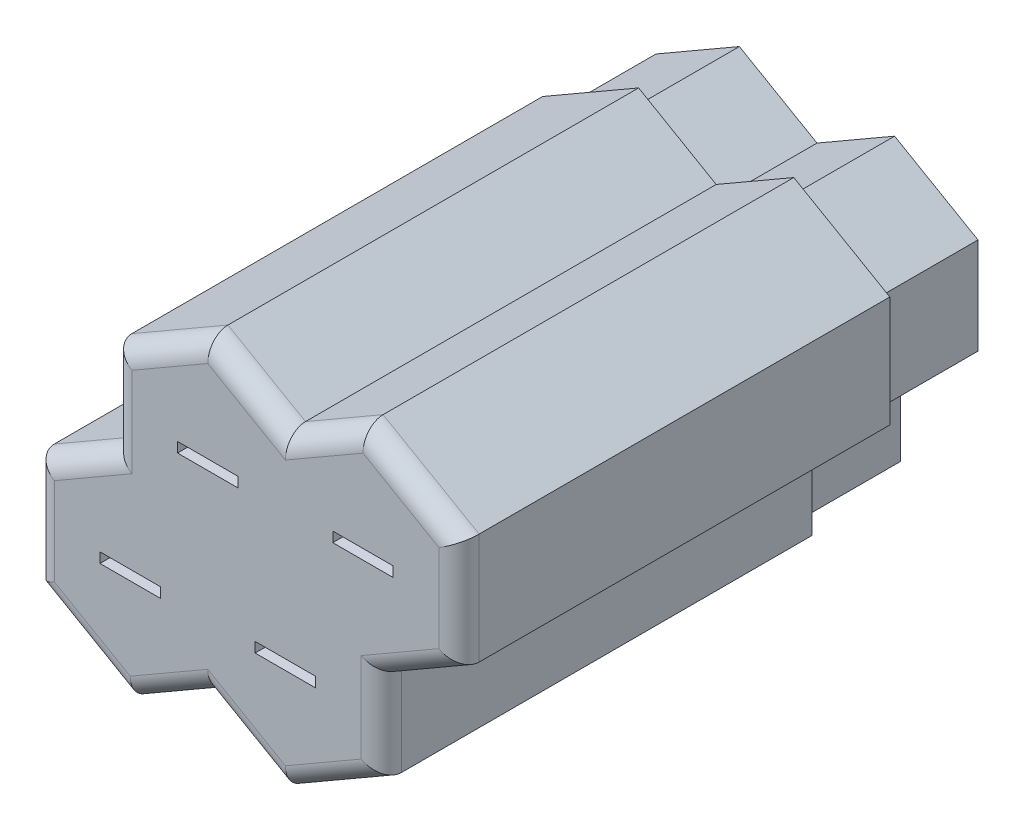
SolidWorks part; units mm, degrees
ref_plane "Ön Düzlem" through (0, 0, 0) normal (0, 0, 1) x (1, 0, 0)
ref_plane "Üst Düzlem" through (0, 0, 0) normal (0, 1, 0) x (1, 0, 0)
ref_plane "Sağ Düzlem" through (0, 0, 0) normal (1, 0, 0) x (0, 0, -1)
sketch "Sketch2" plane through (0, 0, 0) normal (0, 0, 1) x (1, 0, 0)
  line L0 (0, 0) -> (-9.5263, 5.5) construction
  line L1 (0, 11) -> (-9.5263, 5.5)
  line L2 (-9.5263, 5.5) -> (-9.5263, -5.5)
  line L3 (-9.5263, -5.5) -> (0, -11)
  line L4 (0, -11) -> (9.5263, -5.5)
  line L5 (9.5263, -5.5) -> (9.5263, 5.5)
  line L6 (9.5263, 5.5) -> (0, 11)
  line L7 (3, -0.5) -> (-3, -0.5)
  line L8 (3, -0.5) -> (3, 0.5)
  line L9 (3, 0.5) -> (-3, 0.5)
  line L10 (-3, -0.5) -> (-3, 0.5)
  line L11 (3, -0.5) -> (-3, 0.5) construction
  line L12 (3, 0.5) -> (-3, -0.5) construction
  line L13 (2.801, -10.5083) -> (7.7, -7.6799)
  line L14 (0, 0) -> (0, -11) construction
  line L15 (0, 0) -> (9.5263, -5.5) construction
  line L16 (15.4, 5.6569) -> (10.501, 2.8285)
  line L17 (0, 0) -> (0, 11) construction
  line L18 (10.501, 2.8285) -> (10.501, -2.8285)
  line L19 (10.501, -2.8285) -> (15.4, -5.6569)
  line L20 (15.4, -5.6569) -> (20.299, -2.8285)
  line L21 (20.299, -2.8285) -> (20.299, 2.8285)
  line L22 (20.299, 2.8285) -> (15.4, 5.6569)
  line L23 (0, 5.6569) -> (-4.899, 2.8285)
  line L24 (-4.899, 2.8285) -> (-4.899, -2.8285)
  line L25 (-4.899, -2.8285) -> (0, -5.6569)
  line L26 (-1.8263, -7.8368) -> (-1.8263, -18.8368)
  line L27 (0, -5.6569) -> (4.899, -2.8285)
  line L28 (4.899, -2.8285) -> (4.899, 2.8285)
  line L29 (4.899, 2.8285) -> (0, 5.6569)
  line L30 (7.7, -13.3368) -> (7.7, -2.3368) construction
  line L31 (7.7, -13.3368) -> (7.7, -24.3368) construction
  line L32 (2.801, -16.1653) -> (2.801, -10.5083)
  line L33 (7.7, 0) -> (7.7, 14.7115) construction
  line L34 (-9.5263, 2.8285) -> (9.5263, 2.8285)
  line L35 (-9.5263, 2.8285) -> (-9.5263, -2.8285)
  line L36 (7.7, -18.9937) -> (2.801, -16.1653)
  line L37 (-9.5263, -2.8285) -> (9.5263, -2.8285)
  line L38 (9.5263, 2.8285) -> (9.5263, -2.8285)
  line L39 (12.599, -16.1653) -> (7.7, -18.9937)
  line L40 (12.599, -10.5083) -> (12.599, -16.1653)
  line L41 (7.7, -7.6799) -> (12.599, -10.5083)
  line L42 (12.4, -0.5) -> (12.4, -9.2679) construction
  line L43 (7.7, -2.3368) -> (-1.8263, -7.8368)
  line L44 (17.2263, -7.8368) -> (7.7, -2.3368)
  line L45 (17.2263, -18.8368) -> (17.2263, -7.8368)
  line L46 (7.7, -24.3368) -> (17.2263, -18.8368)
  line L47 (-1.8263, -18.8368) -> (7.7, -24.3368)
  line L48 (10.7, -13.8368) -> (4.7, -12.8368) construction
  line L49 (10.7, -12.8368) -> (4.7, -13.8368) construction
  line L50 (4.698, -12.837) -> (10.698, -13.837) construction
  line L51 (4.698, -13.837) -> (10.698, -12.837) construction
  line L52 (4.7, -12.8368) -> (4.7, -13.8368)
  line L53 (10.7, -13.8368) -> (4.7, -13.8368)
  line L54 (10.7, -12.8368) -> (10.7, -13.8368)
  line L55 (10.7, -12.8368) -> (4.7, -12.8368)
  line L56 (18.402, -0.4998) -> (12.402, 0.5002) construction
  line L57 (18.402, 0.5002) -> (12.402, -0.4998) construction
  line L58 (10.698, -13.837) -> (10.698, -12.837)
  line L59 (4.698, -12.837) -> (10.698, -12.837)
  line L60 (4.698, -13.837) -> (4.698, -12.837)
  line L61 (4.698, -13.837) -> (10.698, -13.837)
  line L62 (-3.002, 0.5002) -> (2.998, 0.5002)
  line L63 (-3.002, 0.5002) -> (-3.002, -0.4998)
  line L64 (-3.002, -0.4998) -> (2.998, -0.4998)
  line L65 (2.998, 0.5002) -> (2.998, -0.4998)
  line L66 (-3.002, 0.5002) -> (2.998, -0.4998) construction
  line L67 (-3.002, -0.4998) -> (2.998, 0.5002) construction
  line L68 (-7.7, -13.3368) -> (-7.7, -2.3368) construction
  line L69 (-4.698, -13.837) -> (-10.698, -12.837) construction
  line L70 (-4.698, -12.837) -> (-10.698, -13.837) construction
  line L71 (-10.7, -12.8368) -> (-4.7, -13.8368) construction
  line L72 (-10.7, -13.8368) -> (-4.7, -12.8368) construction
  line L73 (-4.698, -13.837) -> (-10.698, -13.837)
  line L74 (-4.698, -13.837) -> (-4.698, -12.837)
  line L75 (-4.698, -12.837) -> (-10.698, -12.837)
  line L76 (-10.698, -13.837) -> (-10.698, -12.837)
  line L77 (-10.7, -12.8368) -> (-4.7, -12.8368)
  line L78 (-10.7, -12.8368) -> (-10.7, -13.8368)
  line L79 (-10.7, -13.8368) -> (-4.7, -13.8368)
  line L80 (-4.7, -12.8368) -> (-4.7, -13.8368)
  line L81 (-12.599, -16.1653) -> (-7.7, -18.9937)
  line L82 (15.4, 0) -> (15.4, 11) construction
  line L83 (-7.7, -18.9937) -> (-2.801, -16.1653)
  line L84 (15.4, 0) -> (5.8737, -5.5) construction
  line L85 (15.4, 0) -> (15.4, -11) construction
  line L86 (-2.801, -16.1653) -> (-2.801, -10.5083)
  line L87 (12.4, 0.5) -> (18.4, -0.5) construction
  line L88 (12.4, -0.5) -> (18.4, 0.5) construction
  line L89 (15.4, 0) -> (24.9263, 5.5) construction
  line L90 (-2.801, -10.5083) -> (-7.7, -7.6799)
  line L91 (12.402, 0.5002) -> (12.402, -0.4998)
  line L92 (18.402, -0.4998) -> (12.402, -0.4998)
  line L93 (18.402, 0.5002) -> (18.402, -0.4998)
  line L94 (18.402, 0.5002) -> (12.402, 0.5002)
  line L95 (-7.7, -7.6799) -> (-12.599, -10.5083)
  line L96 (-12.599, -10.5083) -> (-12.599, -16.1653)
  line L97 (-17.2263, -7.8368) -> (-7.7, -2.3368)
  line L98 (-7.7, -2.3368) -> (1.8263, -7.8368)
  line L99 (1.8263, -7.8368) -> (1.8263, -18.8368)
  line L100 (-7.7, -13.3368) -> (-7.7, -24.3368) construction
  line L101 (1.8263, -18.8368) -> (-7.7, -24.3368)
  line L102 (-7.7, -24.3368) -> (-17.2263, -18.8368)
  line L103 (-17.2263, -18.8368) -> (-17.2263, -7.8368)
  line L104 (18.402, -0.4998) -> (10.7, -13.8368)
  line L105 (-3.002, -0.4998) -> (-10.7, -12.8368)
  line L107 (17.2263, -10.5083) -> (-17.2263, -10.5083)
  line L108 (17.2263, -10.5083) -> (17.2263, -16.1653)
  line L109 (17.2263, -16.1653) -> (-17.2263, -16.1653)
  line L110 (5.8737, 2.8285) -> (5.8737, -2.8285)
  line L111 (24.9263, -2.8285) -> (5.8737, -2.8285)
  line L112 (-17.2263, -10.5083) -> (-17.2263, -16.1653)
  line L114 (24.9263, 2.8285) -> (24.9263, -2.8285)
  line L115 (-3.002, -0.4998) -> (-3.002, -9.2668) construction
  line L116 (3, -0.5) -> (3, -9.2679) construction
  line L117 (24.9263, 2.8285) -> (5.8737, 2.8285)
  line L121 (18.4, -0.5) -> (18.4, 0.5)
  line L122 (12.4, 0.5) -> (18.4, 0.5)
  line L123 (12.4, -0.5) -> (12.4, 0.5)
  line L124 (12.4, -0.5) -> (18.4, -0.5)
  line L125 (5.8737, 5.5) -> (15.4, 11)
  line L126 (5.8737, -5.5) -> (5.8737, 5.5)
  line L127 (15.4, -11) -> (5.8737, -5.5)
  line L128 (24.9263, -5.5) -> (15.4, -11)
  line L129 (24.9263, 5.5) -> (24.9263, -5.5)
  line L130 (15.4, 11) -> (24.9263, 5.5)
  line L169 (2.3479, -1.9335) -> (-2.8483, 1.0665) [skipped]
  line L170 (2.8479, -1.0675) -> (-2.3483, 1.9325) [skipped]
  line L171 (-2.8483, 1.0665) -> (-2.3483, 1.9325) [skipped]
  line L172 (-0.5011, -3.0009) -> (0.4989, -3.0009) [skipped]
  line L173 (-1.9346, -2.3487) -> (-1.0686, -2.8487) [skipped]
  line L174 (-2.85, -1.0673) -> (-2.35, -1.9333) [skipped]
  line L175 (-2.85, -1.0673) -> (2.3462, 1.9327) [skipped]
  line L176 (-2.35, -1.9333) -> (2.8462, 1.0667) [skipped]
  line L177 (2.348, 1.9335) -> (-2.8481, -1.0665) [skipped]
  line L178 (-2.3481, -1.9325) -> (-2.8481, -1.0665) [skipped]
  line L179 (-1.9346, -2.3487) -> (1.0654, 2.8474) [skipped]
  line L180 (-1.0686, -2.8487) -> (1.9314, 2.3474) [skipped]
  line L181 (-0.5011, -3.0009) -> (-0.5011, 2.9991) [skipped]
  line L182 (0.4989, -3.0009) -> (0.4989, 2.9991) [skipped]
  line L183 (1.0664, -2.8489) -> (-1.9336, 2.3473) [skipped]
  line L184 (-2.8499, 1.0677) -> (2.3463, -1.9323) [skipped]
  line L185 (1.9324, -2.3489) -> (-1.0676, 2.8473) [skipped]
  line L186 (-2.3499, 1.9337) -> (2.8463, -1.0663) [skipped]
  line L187 (2.3462, 1.9327) -> (2.8462, 1.0667) [skipped]
  line L188 (1.0654, 2.8474) -> (1.9314, 2.3474) [skipped]
  line L189 (-0.5011, 2.9991) -> (0.4989, 2.9991) [skipped]
  line L190 (-1.9336, 2.3473) -> (-1.0676, 2.8473) [skipped]
  line L191 (-2.3499, 1.9337) -> (-2.8499, 1.0677) [skipped]
  line L192 (1.0666, 2.849) -> (-1.9334, -2.3472) [skipped]
  line L193 (1.9326, 2.349) -> (-1.0674, -2.8472) [skipped]
  line L194 (2.848, 1.0675) -> (2.348, 1.9335) [skipped]
  line L195 (-2.35, -1.9333) -> (2.3462, 1.9327) construction
  line L196 (2.848, 1.0675) -> (-2.3481, -1.9325) [skipped]
  line L197 (-2.85, -1.0673) -> (2.8462, 1.0667) construction
  line L198 (2.848, 1.0675) -> (-2.8481, -1.0665) construction
  line L199 (2.348, 1.9335) -> (-2.3481, -1.9325) construction
  line L200 (0.4991, 3.0011) -> (0.4991, -2.9989) [skipped]
  line L201 (-0.5011, -3.0009) -> (0.4989, 2.9991) construction
  line L202 (-1.9346, -2.3487) -> (1.9314, 2.3474) construction
  line L203 (-1.0686, -2.8487) -> (1.0654, 2.8474) construction
  line L204 (0.4991, 3.0011) -> (-0.5009, -2.9989) construction
  line L205 (1.9326, 2.349) -> (-1.9334, -2.3472) construction
  line L206 (1.0666, 2.849) -> (-1.0674, -2.8472) construction
  line L207 (1.9326, 2.349) -> (1.0666, 2.849) [skipped]
  line L208 (0.4991, 3.0011) -> (-0.5009, 3.0011) [skipped]
  line L209 (-1.0684, 2.8491) -> (1.9316, -2.347) [skipped]
  line L210 (-1.0684, 2.8491) -> (-1.9344, 2.3491) [skipped]
  line L211 (-1.9344, 2.3491) -> (1.0656, -2.847) [skipped]
  line L212 (-0.5009, 3.0011) -> (-0.5009, -2.9989) [skipped]
  line L213 (2.3479, -1.9335) -> (-2.3483, 1.9325) construction
  line L214 (1.0664, -2.8489) -> (-1.0676, 2.8473) construction
  line L215 (1.9324, -2.3489) -> (-1.9336, 2.3473) construction
  line L216 (0.4989, -3.0009) -> (-0.5011, 2.9991) construction
  line L217 (-2.3499, 1.9337) -> (2.3463, -1.9323) construction
  line L218 (-1.0684, 2.8491) -> (1.0656, -2.847) construction
  line L219 (-1.9344, 2.3491) -> (1.9316, -2.347) construction
  line L220 (-0.5009, 3.0011) -> (0.4991, -2.9989) construction
  line L221 (2.8479, -1.0675) -> (-2.8483, 1.0665) construction
  line L222 (-2.8499, 1.0677) -> (2.8463, -1.0663) construction
  line L223 (2.3479, -1.9335) -> (2.8479, -1.0675) [skipped]
  line L224 (2.8463, -1.0663) -> (2.3463, -1.9323) [skipped]
  line L225 (1.0664, -2.8489) -> (1.9324, -2.3489) [skipped]
  line L226 (0.4991, -2.9989) -> (-0.5009, -2.9989) [skipped]
  line L227 (-1.0674, -2.8472) -> (-1.9334, -2.3472) [skipped]
  line L228 (1.9316, -2.347) -> (1.0656, -2.847) [skipped]
  circle A0 centre (0, 0) radius 4.899 construction
  circle A1 centre (0, 0) radius 7.7
  circle A2 centre (15.4, 0) radius 5.6569
  circle A3 centre (15.4, 0) radius 7.7
  circle A4 centre (0, 0) radius 5.6569
  circle A5 centre (7.7, -13.3368) radius 4.899 construction
  circle A6 centre (7.7, -13.3368) radius 5.6569
  circle A7 centre (7.7, -13.3368) radius 7.7
  circle A8 centre (-7.7, -13.3368) radius 4.899 construction
  circle A9 centre (-7.7, -13.3368) radius 5.6569
  circle A10 centre (15.4, 0) radius 4.899 construction
  circle A11 centre (-7.7, -13.3368) radius 7.7
  dimension "D1" = 15.4
  dimension "D3" = 6
  dimension "D6" = 12
extrude "Boss-Extrude1" add sketch "Sketch2" along normal blind 2.25 contours L128 L127 L126 L125 L130 L129 | L2 L3 L4 L5 L6 L1 | L9 L10 L7 L8 | L94 L91 L92 L93 | L103 L97 L98 L99 L101 L102 | L47 L46 L45 L44 L43 L26 | L54 L55 L52 L53 | L75 L76 L73 L74
extrude "Boss-Extrude2" add sketch "Sketch2<4>" against normal blind 50.5 contours L5 A3 L117 L129 L130 L125 L6 | A1 L126 L125 L6 L1 L2 L34 | L117 A3 L111 L114 | L111 A3 L44 L45 L128 L129 | A7 L127 L128 L45 L44 A3 L104 | A7 L99 L101 L47 L46 L45 L128 L127 | A7 A11 L26 L47 L101 L99 | L26 A11 L3 L2 L97 L103 L102 L101 L47 | A1 L34 L2 L37 L97 L98 | L3 A11 L105 A1 L37 L97 L2 | L117 A3 L5 L6 L125 L126 A1 | A7 L4 L5 A3 L111 A1 L126 L127 | L26 A11 L3 L4 A7 L99 L98 A1 L43 | A1 L98 L97 L37 | L2 L97 L37 | A7 L109 L45 L107 L128 L127 | L109 A11 L107 L103 | L107 A11 L3 L2 L97 L103 | L111 A3 L44 L43 A1 | L107 A11 L3 L4 A7 | A7 L127 L128 L107 | L45 L128 L107 region at (3.7547, 8.6121, 0) region at (11.6453, 8.6121, 0) region at (7.7, 4.753, 0) region at (-8.5449, 0.0928, 0) region at (-9.2014, -3.016, 0) region at (-7.918, -4.3988, 0) region at (-13.7224, -7.2572, 0) region at (-7.7583, -2.6563, 0) region at (23.9184, 0, 0) region at (21.4224, -6.0796, 0) region at (-16.2184, -13.3368, 0) region at (7.7, -2.6464, 0) region at (-16.044, -16.3559, 0) region at (7.7, -4.5314, 0) region at (15.6804, -8.9709, 0) region at (16.9014, -10.3207, 0) region at (0, -8.8053, 0) region at (16.2449, -13.4295, 0) region at (15.4583, -10.6805, 0) region at (0, -18.0898, 0) region at (0, -10.6904, 0) region at (17.0356, -17.501, 0)
sketch "Sketch2<4>" plane through (0, 0, 0) normal (0, 0, 1) x (1, 0, 0) same geometry as "Sketch2"
extrude "Cut-Extrude1" cut sketch "Sketch2<5>" along normal blind 0.25 contours A2 | A4 | A6 | A9
sketch "Sketch2<5>" plane through (0, 0, 0) normal (0, 0, 1) x (1, 0, 0) same geometry as "Sketch2"
fillet "Fillet1" radius 2 14 edges at (3.85, 8.7772, 2.25) (20.1631, 8.25, 2.25) (11.55, 8.7772, 2.25) (24.9263, 0, 2.25) (21.0763, -7.7228, 2.25) (17.2263, -14.3912, 2.25) (12.4631, -21.5868, 2.25) (3.85, -22.114, 2.25) (-3.85, -22.114, 2.25) (-12.4631, -21.5868, 2.25) (-17.2263, -13.3368, 2.25) (-13.3763, -5.614, 2.25) (-9.5263, 1.0544, 2.25) (-4.7631, 8.25, 2.25)
sketch "Sketch7" plane through (0, 0, -50.5) normal (0, 0, -1) x (-1, 0, 0)
  line L0 (-24.9263, 5.5) -> (-24.9263, -5.5)
  line L1 (-7.7, 5.111) -> (-15.4, 9.5566)
  line L2 (-15.4, 9.5566) -> (-23.6763, 4.7783)
  line L3 (-23.6763, 4.7783) -> (-23.6763, -4.7783)
  line L4 (-23.6763, -4.7783) -> (-15.9763, -9.2239)
  line L5 (-15.9763, -18.1151) -> (-15.9763, -9.2239)
  line L6 (-7.7, -22.8934) -> (-15.9763, -18.1151)
  line L7 (0, -18.4478) -> (-7.7, -22.8934)
  line L8 (0, -18.4478) -> (7.7, -22.8934)
  line L9 (7.7, -22.8934) -> (15.9763, -18.1151)
  line L10 (15.9763, -18.1151) -> (15.9763, -8.5585)
  line L11 (15.9763, -8.5585) -> (8.2763, -4.1129)
  line L12 (8.2763, 4.7783) -> (8.2763, -4.1129)
  line L13 (0, 9.5566) -> (8.2763, 4.7783)
  line L14 (-7.7, 5.111) -> (0, 9.5566)
  line L130 (-12.4, -0.5) -> (-18.4, 0.5) construction
  line L131 (-12.4, 0.5) -> (-18.4, -0.5) construction
  line L135 (10.7, -13.8368) -> (4.7, -12.8368) construction
  line L136 (10.7, -12.8368) -> (4.7, -13.8368) construction
  line L137 (4.698, -12.837) -> (10.698, -13.837) construction
  line L138 (4.698, -13.837) -> (10.698, -12.837) construction
  line L140 (3.002, -0.4998) -> (-2.998, 0.5002) construction
  line L141 (3.002, 0.5002) -> (-2.998, -0.4998) construction
  line L142 (-18.402, 0.5002) -> (-12.402, -0.4998) construction
  line L143 (-18.402, -0.4998) -> (-12.402, 0.5002) construction
  line L144 (-4.698, -13.837) -> (-10.698, -12.837) construction
  line L145 (-4.698, -12.837) -> (-10.698, -13.837) construction
  line L146 (-10.7, -12.8368) -> (-4.7, -13.8368) construction
  line L147 (-10.7, -13.8368) -> (-4.7, -12.8368) construction
  line L155 (-3, 0.5) -> (3, -0.5) construction
  line L156 (-3, -0.5) -> (3, 0.5) construction
  line L158 (-15.4, 11) -> (-24.9263, 5.5)
  line L159 (-24.9263, -5.5) -> (-17.2263, -9.9456)
  line L162 (-7.7, 6.5544) -> (-15.4, 11)
  line L163 (-12.4, -0.5) -> (-18.4, -0.5)
  line L164 (-12.4, -0.5) -> (-12.4, 0.5)
  line L165 (-12.4, 0.5) -> (-18.4, 0.5)
  line L166 (-18.4, -0.5) -> (-18.4, 0.5)
  line L174 (17.2263, -18.8368) -> (17.2263, -7.8368)
  line L175 (7.7, -24.3368) -> (17.2263, -18.8368)
  line L176 (0, -19.8912) -> (7.7, -24.3368)
  line L179 (17.2263, -7.8368) -> (9.5263, -3.3912)
  line L180 (12.599, -10.5083) -> (12.599, -16.1653)
  line L181 (7.7, -7.6799) -> (12.599, -10.5083)
  line L182 (-18.402, 0.5002) -> (-12.402, 0.5002)
  line L183 (-18.402, 0.5002) -> (-18.402, -0.4998)
  line L184 (-18.402, -0.4998) -> (-12.402, -0.4998)
  line L185 (-12.402, 0.5002) -> (-12.402, -0.4998)
  line L186 (2.801, -10.5083) -> (7.7, -7.6799)
  line L187 (2.801, -16.1653) -> (2.801, -10.5083)
  line L188 (7.7, -18.9937) -> (2.801, -16.1653)
  line L189 (12.599, -16.1653) -> (7.7, -18.9937)
  line L190 (4.7, -12.8368) -> (4.7, -13.8368)
  line L191 (10.7, -13.8368) -> (4.7, -13.8368)
  line L192 (10.7, -12.8368) -> (10.7, -13.8368)
  line L193 (10.7, -12.8368) -> (4.7, -12.8368)
  line L194 (10.698, -13.837) -> (10.698, -12.837)
  line L195 (4.698, -12.837) -> (10.698, -12.837)
  line L196 (4.698, -13.837) -> (4.698, -12.837)
  line L197 (4.698, -13.837) -> (10.698, -13.837)
  line L198 (-2.998, 0.5002) -> (-2.998, -0.4998)
  line L199 (3.002, -0.4998) -> (-2.998, -0.4998)
  line L200 (3.002, 0.5002) -> (3.002, -0.4998)
  line L201 (3.002, 0.5002) -> (-2.998, 0.5002)
  line L202 (-4.698, -13.837) -> (-10.698, -13.837)
  line L203 (-4.698, -13.837) -> (-4.698, -12.837)
  line L204 (-4.698, -12.837) -> (-10.698, -12.837)
  line L205 (-10.698, -13.837) -> (-10.698, -12.837)
  line L206 (-10.7, -12.8368) -> (-4.7, -12.8368)
  line L207 (-10.7, -12.8368) -> (-10.7, -13.8368)
  line L208 (-10.7, -13.8368) -> (-4.7, -13.8368)
  line L209 (-4.7, -12.8368) -> (-4.7, -13.8368)
  line L210 (0, -19.8912) -> (-7.7, -24.3368)
  line L211 (-7.7, -24.3368) -> (-17.2263, -18.8368)
  line L212 (-17.2263, -18.8368) -> (-17.2263, -9.9456)
  line L215 (-7.7, -7.6799) -> (-12.599, -10.5083)
  line L216 (-12.599, -10.5083) -> (-12.599, -16.1653)
  line L217 (-12.599, -16.1653) -> (-7.7, -18.9937)
  line L220 (-7.7, -18.9937) -> (-2.801, -16.1653)
  line L223 (-2.801, -16.1653) -> (-2.801, -10.5083)
  line L224 (-4.899, 2.8285) -> (0, 5.6569)
  line L225 (-4.899, -2.8285) -> (-4.899, 2.8285)
  line L226 (0, -5.6569) -> (-4.899, -2.8285)
  line L228 (4.899, -2.8285) -> (0, -5.6569)
  line L229 (4.899, 2.8285) -> (4.899, -2.8285)
  line L230 (0, 5.6569) -> (4.899, 2.8285)
  line L231 (-20.299, 2.8285) -> (-15.4, 5.6569)
  line L232 (-20.299, -2.8285) -> (-20.299, 2.8285)
  line L233 (-15.4, -5.6569) -> (-20.299, -2.8285)
  line L234 (-10.501, -2.8285) -> (-15.4, -5.6569)
  line L235 (-10.501, 2.8285) -> (-10.501, -2.8285)
  line L236 (-15.4, 5.6569) -> (-10.501, 2.8285)
  line L237 (-2.801, -10.5083) -> (-7.7, -7.6799)
  line L238 (3, -0.5) -> (3, 0.5)
  line L239 (-3, 0.5) -> (3, 0.5)
  line L240 (-3, -0.5) -> (-3, 0.5)
  line L241 (-3, -0.5) -> (3, -0.5)
  line L242 (-7.7, 6.5544) -> (0, 11)
  line L246 (9.5263, 5.5) -> (9.5263, -3.3912)
  line L247 (0, 11) -> (9.5263, 5.5)
  circle A12 centre (-15.4, 0) radius 4.899 construction
  circle A13 centre (7.7, -13.3368) radius 4.899 construction
  circle A14 centre (-7.7, -13.3368) radius 4.899 construction
  circle A15 centre (0, 0) radius 4.899 construction
  circle A16 centre (7.7, -13.3368) radius 7.7
  circle A18 centre (-7.7, -13.3368) radius 7.7
  circle A21 centre (-15.4, 0) radius 7.7
  circle A23 centre (0, 0) radius 7.7
  line M9 (0, -19.8912) -> (7.7, -24.3368)
  line M10 (7.7, -24.3368) -> (17.2263, -18.8368)
  line M11 (17.2263, -18.8368) -> (17.2263, -7.8368)
  line M12 (17.2263, -7.8368) -> (9.5263, -3.3912)
  line M13 (9.5263, -3.3912) -> (9.5263, 5.5)
  line M14 (9.5263, 5.5) -> (0, 11)
  line M15 (0, 11) -> (-7.7, 6.5544)
  line M16 (-7.7, 6.5544) -> (-15.4, 11)
  line M17 (-15.4, 11) -> (-24.9263, 5.5)
  line M18 (-24.9263, 5.5) -> (-24.9263, -5.5)
  line M19 (-24.9263, -5.5) -> (-17.2263, -9.9456)
  line M20 (-17.2263, -9.9456) -> (-17.2263, -18.8368)
  line M21 (-17.2263, -18.8368) -> (-7.7, -24.3368)
  line M22 (-7.7, -24.3368) -> (0, -19.8912)
  dimension "D1" = 1.25
extrude "Cut-Extrude3" cut sketch "Sketch7" against normal blind 10 contours L1 L14 L13 L12 L11 L10 L9 L8 L7 L6 L5 L4 L3 L2 M22 M9 M10 M11 M12 M13 M14 M15 M16 M17 M18 M19 M20 M21 region at (19.8881, 7.7736, -50.5)
